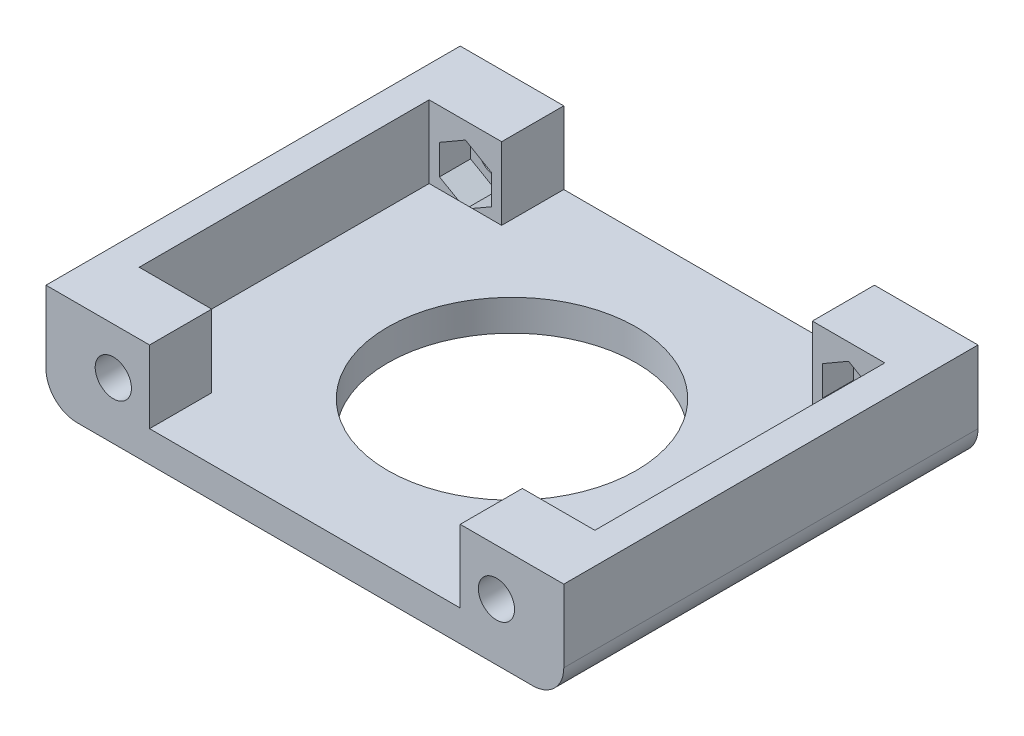
SolidWorks part; units mm, degrees
ref_plane "Front Plane" through (0, 0, 0) normal (0, 0, 1) x (1, 0, 0)
ref_plane "Top Plane" through (0, 0, 0) normal (0, 1, 0) x (1, 0, 0)
ref_plane "Right Plane" through (0, 0, 0) normal (1, 0, 0) x (0, 0, -1)
sketch "Sketch1" plane through (0, 0, 0) normal (0, 1, 0) x (1, 0, 0)
  line L1 (-25, 20) -> (25, 20)
  line L2 (-25, 20) -> (-25, -20)
  line L3 (-25, -20) -> (25, -20)
  line L4 (25, 20) -> (25, -20)
  line L5 (-25, 20) -> (25, -20) construction
  line L6 (-25, -20) -> (25, 20) construction
  point P0 (0, 0)
  dimension "D1" = 50
  dimension "D2" = 40
extrude "Boss-Extrude1" add sketch "Sketch1" along normal blind 3
sketch "Sketch2" plane through (0, 3, 0) normal (0, 1, 0) x (1, 0, 0)
  circle A0 centre (0, 0) radius 12
  dimension "D1" = 24
extrude "Cut-Extrude1" cut sketch "Sketch2" against normal through all
sketch "Sketch3" plane through (0, 3, 0) normal (0, 1, 0) x (1, 0, 0)
  line L0 (-25, -20) -> (25, -20) construction
  line L1 (-25, 20) -> (-22, 20)
  line L2 (-25, 20) -> (-25, -20)
  line L3 (-25, -20) -> (-22, -20)
  line L4 (-22, 20) -> (-22, -20)
  line L6 (22, -20) -> (25, -20)
  line L7 (22, -20) -> (22, 20)
  line L8 (22, 20) -> (25, 20)
  line L9 (25, -20) -> (25, 20)
  dimension "D1" = 3
extrude "Boss-Extrude2" add sketch "Sketch3" along normal blind 7
sketch "Sketch4" plane through (0, 0, 20) normal (0, 0, 1) x (1, 0, 0)
  line L1 (-22, 3) -> (-15, 3)
  line L2 (-22, 3) -> (-22, 10)
  line L3 (-22, 10) -> (-15, 10)
  line L4 (-15, 3) -> (-15, 10)
  line L5 (22, 3) -> (15, 3)
  line L6 (22, 3) -> (22, 10)
  line L7 (22, 10) -> (15, 10)
  line L8 (15, 3) -> (15, 10)
  dimension "D2" = 7
  dimension "6" = 7
extrude "Boss-Extrude3" add sketch "Sketch4" against normal blind 6
sketch "Sketch5" plane through (0, 0, 20) normal (0, 0, 1) x (1, 0, 0)
  line L0 (-18.5, 10) -> (-18.5, 5.5) construction
  line L2 (18.5, 10) -> (18.5, 5.5) construction
  line L3 (-25, 0) -> (25, 0) construction
  line L4 (-18.5, 5.5) -> (18.5, 5.5) construction
  line L6 (-22, 10) -> (-15, 10) construction
  line L7 (-25, 10) -> (-15, 10) construction
  line L8 (15, 10) -> (22, 10) construction
  line L9 (15, 10) -> (15, 3) construction
  line L10 (15, 10) -> (25, 10) construction
  circle A0 centre (-18.5, 5.5) radius 1.75
  circle A1 centre (18.5, 5.5) radius 1.75
  dimension "D1" = 3.5
  dimension "D2" = 3.5
  dimension "D3" = 5.5
extrude "Cut-Extrude2" cut sketch "Sketch5" against normal through all
mirror "Mirror1" about plane through (0, 0, 0) normal (0, 0, 1) of "Cut-Extrude2", "Boss-Extrude3"
sketch "Sketch6" plane through (0, 0, -14) normal (0, 0, 1) x (1, 0, 0)
  line L1 (-18.5, 2.6132) -> (-16, 4.0566)
  line L2 (-16, 4.0566) -> (-16, 6.9434)
  line L3 (-16, 6.9434) -> (-18.5, 8.3868)
  line L4 (-18.5, 8.3868) -> (-21, 6.9434)
  line L5 (-21, 6.9434) -> (-21, 4.0566)
  line L6 (-21, 4.0566) -> (-18.5, 2.6132)
  circle A0 centre (-18.5, 5.5) radius 2.5 construction
  dimension "D1" = 5
extrude "Cut-Extrude3" cut sketch "Sketch6" against normal blind 3
mirror "Mirror2" about plane through (0, 0, 0) normal (1, 0, 0) of "Cut-Extrude3"
mirror "Mirror3" about plane through (0, 0, 0) normal (0, 0, 1) of "Mirror2"
fillet "Fillet1" radius 3 2 edges at (-25, 0, 0) (25, 0, 0)
